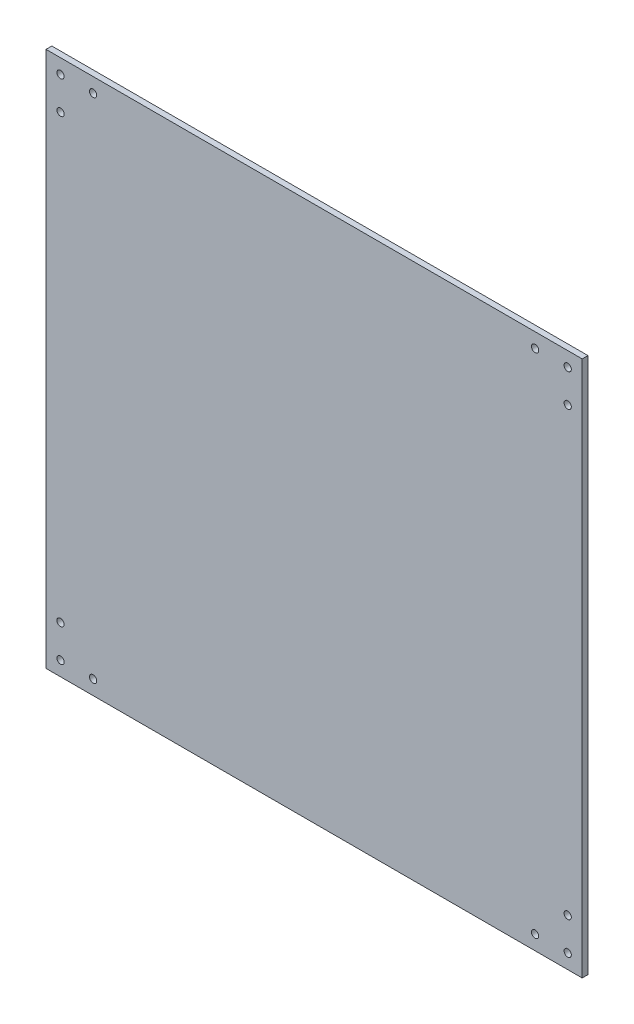
SolidWorks part; units mm, degrees
ref_plane "前视基准面" through (0, 0, 0) normal (0, 0, 1) x (1, 0, 0)
ref_plane "上视基准面" through (0, 0, 0) normal (0, 1, 0) x (1, 0, 0)
ref_plane "右视基准面" through (0, 0, 0) normal (1, 0, 0) x (0, 0, -1)
sketch "草图1" plane through (0, 0, 0) normal (0, 0, 1) x (1, 0, 0)
  line L1 (185, -185) -> (-185, -185)
  line L2 (185, -185) -> (185, 185)
  line L3 (185, 185) -> (-185, 185)
  line L4 (-185, -185) -> (-185, 185)
  line L5 (185, -185) -> (-185, 185) construction
  line L6 (185, 185) -> (-185, -185) construction
  point P0 (0, 0)
  dimension "D1" = 370
  dimension "D2" = 370
extrude "凸台-拉伸1" add sketch "草图1" along normal blind 4
sketch "草图2" plane through (0, 0, 4) normal (0, 0, 1) x (1, 0, 0)
  line L0 (-165, -175) -> (-152.5, -175) construction
  line L1 (-185, -185) -> (-165, -185) construction
  line L2 (-185, -185) -> (-185, -165) construction
  line L3 (-185, -165) -> (-165, -165) construction
  line L4 (-165, -185) -> (-165, -165) construction
  line L5 (-175, -165) -> (-175, -152.5) construction
  circle A0 centre (-175, -175) radius 2.5
  circle A1 centre (-152.5, -175) radius 2.5
  circle A2 centre (-175, -152.5) radius 2.5
  circle A3 centre (-152.5, 175) radius 2.5
  circle A4 centre (-175, 152.5) radius 2.5
  circle A5 centre (-175, 175) radius 2.5
  circle A6 centre (175, 152.5) radius 2.5
  circle A7 centre (152.5, 175) radius 2.5
  circle A8 centre (175, 175) radius 2.5
  circle A9 centre (152.5, -175) radius 2.5
  circle A10 centre (175, -152.5) radius 2.5
  circle A11 centre (175, -175) radius 2.5
  point P34 (0, 0)
  dimension "D3" = 10
  dimension "D4" = 10
  dimension "D5" = 5
  dimension "D6" = 12.5
  dimension "D7" = 5
  dimension "D9" = 5
  dimension "D1" = 20
  dimension "D2" = 20
  dimension "D8" = 12.5
  dimension "D10" = 4
extrude "切除-拉伸1" cut sketch "草图2" against normal through all
